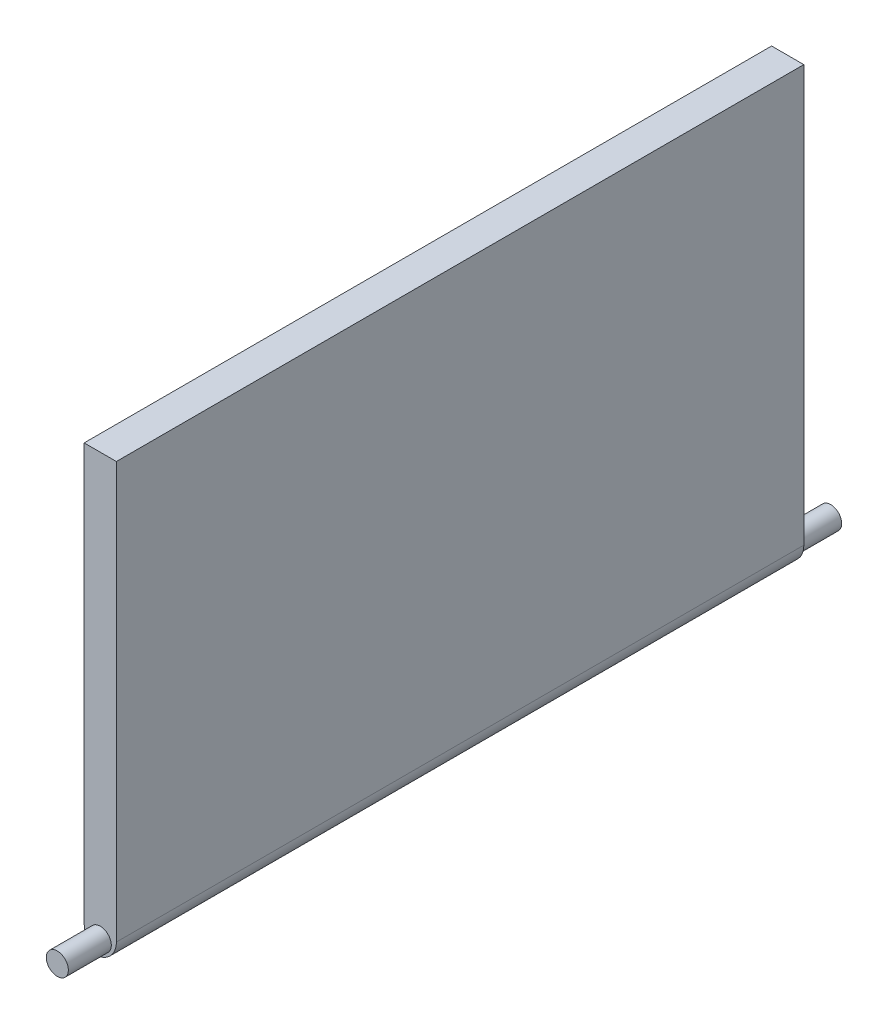
SolidWorks part; units mm, degrees
ref_plane "Front Plane" through (0, 0, 0) normal (0, 0, 1) x (1, 0, 0)
ref_plane "Top Plane" through (0, 0, 0) normal (0, 1, 0) x (1, 0, 0)
ref_plane "Right Plane" through (0, 0, 0) normal (1, 0, 0) x (0, 0, -1)
sketch "Sketch1" plane through (0, 0, 0) normal (1, 0, 0) x (0, 0, -1)
  line L0 (-50.8, -5.3494) -> (-50.8, 3.0258) construction
  line L1 (50.8, 59.3364) -> (-50.8, 59.3364)
  line L2 (50.8, 59.3364) -> (50.8, -5.3464)
  line L3 (50.8, -5.3464) -> (-50.8, -5.3464)
  line L4 (-50.8, 59.3364) -> (-50.8, -5.3464)
  line L5 (-46.0375, -5.3464) -> (46.0375, -5.3464) construction
extrude "Boss-Extrude1" add sketch "Sketch1" against normal blind 4.7625
sketch "Sketch2" plane through (0, 0, 50.8) normal (0, 0, 1) x (1, 0, 0)
  line L0 (-4.7625, -5.3464) -> (0, -5.3464) construction
  circle A0 centre (-2.3813, -2.9652) radius 1.6312
  point P5 (-2.3813, -5.3464)
  dimension "D1" = 2.3813
extrude "Boss-Extrude2" add sketch "Sketch2" along normal blind 6.35
mirror "Mirror1" about plane through (0, 0, 0) normal (0, 0, 1) of "Boss-Extrude2"
fillet "Fillet2" radius 3.175 2 edges at (0, -5.3464, 0) (-4.7625, -5.3464, 0)
